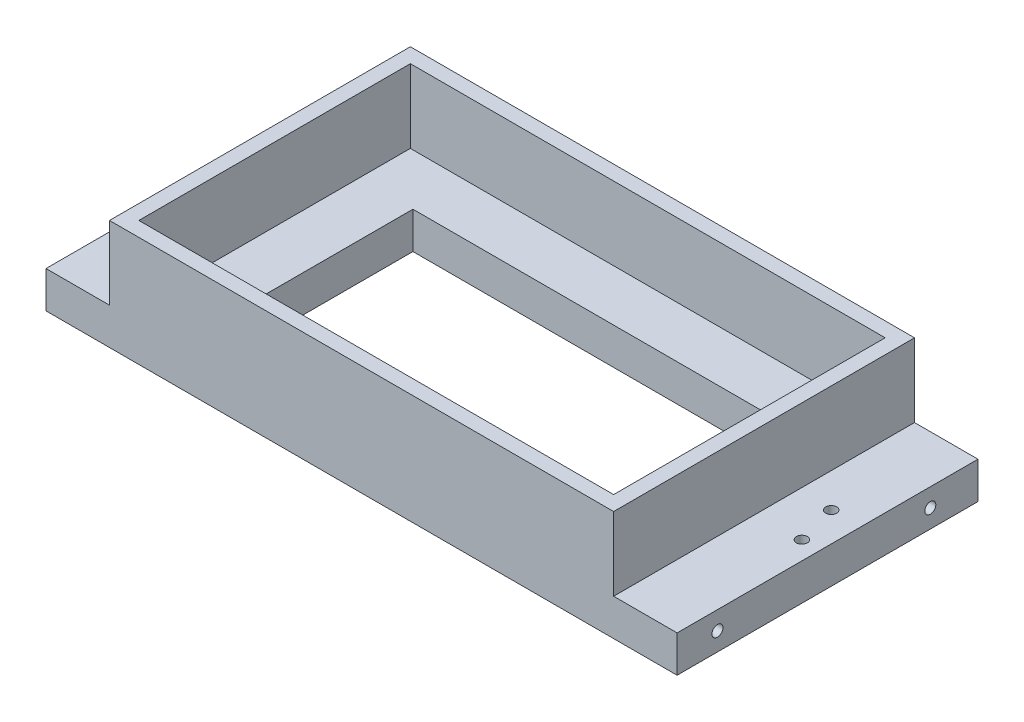
SolidWorks part; units mm, degrees
ref_plane "前视基准面" through (0, 0, 0) normal (0, 0, 1) x (1, 0, 0)
ref_plane "上视基准面" through (0, 0, 0) normal (0, 1, 0) x (1, 0, 0)
ref_plane "右视基准面" through (0, 0, 0) normal (1, 0, 0) x (0, 0, -1)
other "Configuration Table"
sketch "草图1" plane through (0, 0, 0) normal (0, 1, 0) x (1, 0, 0)
  line L1 (-43, -60.5) -> (43, -60.5)
  line L2 (-43, -60.5) -> (-43, 60.5)
  line L3 (-43, 60.5) -> (43, 60.5)
  line L4 (43, -60.5) -> (43, 60.5)
  line L5 (-43, -60.5) -> (43, 60.5) construction
  line L6 (-43, 60.5) -> (43, -60.5) construction
  line L7 (-25, 50.5) -> (25, 50.5)
  line L8 (-25, 50.5) -> (-25, -4.5)
  line L9 (-25, -4.5) -> (25, -4.5)
  line L10 (25, 50.5) -> (25, -4.5)
  line L11 (-25, -25.5) -> (25, -25.5)
  line L12 (-25, -25.5) -> (-25, -50.5)
  line L13 (-25, -50.5) -> (25, -50.5)
  line L14 (25, -25.5) -> (25, -50.5)
  line L15 (-43, -60.5) -> (43, -60.5)
  line L16 (-43, -60.5) -> (-43, -113.5)
  line L17 (-43, -113.5) -> (43, -113.5)
  line L18 (43, -60.5) -> (43, -113.5)
  line L19 (-38, -65.5) -> (38, -65.5)
  line L20 (-38, -65.5) -> (-38, -108.5)
  line L21 (-38, -108.5) -> (38, -108.5)
  line L22 (38, -65.5) -> (38, -108.5)
  point P0 (0, 0)
  dimension "D1" = 86
  dimension "D2" = 121
  dimension "D3" = 10
  dimension "D4" = 18
  dimension "D5" = 18
  dimension "D6" = 55
  dimension "D7" = 10
  dimension "D8" = 25
  dimension "D9" = 5
  dimension "D10" = 5
  dimension "D11" = 5
  dimension "D12" = 5
  dimension "D13" = 53
extrude "凸台-拉伸1" add sketch "草图1" along normal blind 5 contours L18 L1 L16 L17 L19 L22 L21 L20 | L2 L3 L4 L1 | L9 L10 L7 L8 | L11 L14 L13 L12 region at (0, 0, 61.5102)
sketch "草图4" plane through (0, 5, 0) normal (0, 1, 0) x (1, 0, 0)
  line L0 (-43, 60.5) -> (43, 60.5) construction
  line L1 (-34.35, 57.5) -> (34.35, 57.5)
  line L2 (-34.35, 57.5) -> (-34.35, -57.5)
  line L3 (-34.35, -57.5) -> (34.35, -57.5)
  line L4 (34.35, 57.5) -> (34.35, -57.5)
  line L5 (-32.35, -18.5) -> (32.35, -18.5)
  line L6 (-32.35, -18.5) -> (-32.35, -55.5)
  line L7 (-32.35, -55.5) -> (32.35, -55.5)
  line L8 (32.35, -18.5) -> (32.35, -55.5)
  line L9 (32.35, -14.5) -> (-32.35, -14.5)
  line L10 (32.35, -14.5) -> (32.35, 55.5)
  line L11 (32.35, 55.5) -> (-32.35, 55.5)
  line L12 (-32.35, -14.5) -> (-32.35, 55.5)
  line L13 (43, 60.5) -> (43, -113.5) construction
  line L14 (-43, 60.5) -> (-43, -113.5) construction
  dimension "D1" = 5
  dimension "D2" = 10.65
  dimension "D3" = 10.65
  dimension "D4" = 2
  dimension "D5" = 2
  dimension "D6" = 2
  dimension "D7" = 70
  dimension "D8" = 79
  dimension "D9" = 37
  dimension "D10" = 2
extrude "凸台-拉伸2" add sketch "草图4" along normal blind 10 contours L3 L4 L1 L2 | L6 L7 L8 L5 | L12 L11 L10 L9
sketch "草图5" plane through (0, 5, 0) normal (0, 1, 0) x (1, 0, 0)
  line L0 (-43, 60.5) -> (-43, -113.5) construction
  line L1 (43, 60.5) -> (43, -113.5) construction
  line L2 (-43, 60.5) -> (43, 60.5) construction
  line L3 (-43, -85.5) -> (-38, -85.5)
  line L4 (-38, -65.5) -> (-38, -108.5) construction
  line L5 (-23.6333, -57.5) -> (-23.6333, -113.5)
  line L6 (-34.35, -57.5) -> (34.35, -57.5) construction
  line L7 (-43, -113.5) -> (43, -113.5) construction
  line L8 (38, -85.5) -> (43, -85.5)
  line L9 (38, -65.5) -> (38, -108.5) construction
  line L10 (-25, -25.5) -> (-25, -50.5) construction
  line L12 (-34.35, 57.5) -> (34.35, 57.5) construction
  line L13 (-25, -4.5) -> (25, -4.5) construction
  circle A0 centre (-39, 20.5) radius 0.75
  circle A1 centre (39, 20.5) radius 0.75
  circle A2 centre (-39, -32.5) radius 0.75
  circle A3 centre (39, -32.5) radius 0.75
  circle A4 centre (-40.1428, -60.35) radius 0.75
  circle A5 centre (40.1428, -60.35) radius 0.75
  circle A6 centre (-40.1428, -110.5303) radius 0.75
  circle A7 centre (40.1428, -110.5303) radius 0.75
  circle A8 centre (-40.5, 57.5) radius 0.75
  circle A9 centre (-40.5, -38) radius 0.75
  circle A10 centre (-40.5, -85.5) radius 0.75
  circle A11 centre (40.5, 57.5) radius 0.75
  circle A12 centre (40.5, -38) radius 0.75
  circle A13 centre (40.5, -85.5) radius 0.75
  circle A14 centre (-40.5, -4.5) radius 0.75
  circle A15 centre (40.5, -4.5) radius 0.75
  point P40 (-23.6333, -85.5)
  point P52 (-25, -38)
  dimension "D1" = 1.5
  dimension "D2" = 4
  dimension "D3" = 4
  dimension "D4" = 40
  dimension "D5" = 93
extrude "切除-拉伸1" cut sketch "草图5" against normal through all contours A0 | A2 | A4 | A6 | A7 | A5 | A3 | A1 | A8 | A11 | A9 | A12 | A10 | A13 | A14 | A15
sketch "草图7" plane through (0, 5, 0) normal (0, 1, 0) x (1, 0, 0)
  line L0 (42.9928, -57.5) -> (-42.9928, -57.5) construction
  line L1 (-32, -57.5) -> (-17, -57.5)
  line L2 (-32, -57.5) -> (-32, -65.5)
  line L3 (-32, -65.5) -> (-17, -65.5)
  line L4 (-17, -57.5) -> (-17, -65.5)
  line L5 (-43, 60.5) -> (-43, -113.5) construction
  line L6 (-38, -65.5) -> (38, -65.5) construction
  line L8 (-34.35, -57.5) -> (34.35, -57.5) construction
  line L9 (-13, -57.5) -> (13, -57.5)
  line L10 (-13, -57.5) -> (-13, -65.5)
  line L11 (-13, -65.5) -> (13, -65.5)
  line L12 (13, -57.5) -> (13, -65.5)
  line L13 (-38, -65.5) -> (-38, -108.5) construction
  line L14 (-43, -73.5) -> (-38, -73.5)
  line L15 (-43, -73.5) -> (-43, -83.5)
  line L16 (-43, -83.5) -> (-38, -83.5)
  line L17 (-38, -73.5) -> (-38, -83.5)
  line L18 (-43, -113.5) -> (43, -113.5) construction
  line L19 (-43, -95.3803) -> (-38, -95.3803)
  line L20 (-43, -95.3803) -> (-43, -107.5)
  line L21 (-43, -107.5) -> (-38, -107.5)
  line L22 (-38, -95.3803) -> (-38, -107.5)
  line L23 (-42.9928, -113.3803) -> (42.9928, -113.3803) construction
  line L24 (-38, -108.5) -> (38, -108.5) construction
  line L25 (-35, -108.5) -> (-29, -108.5)
  line L26 (-35, -108.5) -> (-35, -113.5)
  line L27 (-35, -113.5) -> (-29, -113.5)
  line L28 (-29, -108.5) -> (-29, -113.5)
  line L29 (43, 60.5) -> (43, -113.5) construction
  line L30 (-6, -108.5) -> (0, -108.5)
  line L31 (-6, -108.5) -> (-6, -113.5)
  line L32 (-6, -113.5) -> (0, -113.5)
  line L33 (0, -108.5) -> (0, -113.5)
  line L34 (14, -108.5) -> (21, -108.5)
  line L35 (14, -108.5) -> (14, -113.5)
  line L36 (14, -113.5) -> (21, -113.5)
  line L37 (21, -108.5) -> (21, -113.5)
  line L38 (27, -108.5) -> (34, -108.5)
  line L39 (27, -108.5) -> (27, -113.5)
  line L40 (27, -113.5) -> (34, -113.5)
  line L41 (34, -108.5) -> (34, -113.5)
  line L42 (43, -81.5) -> (38, -81.5)
  line L43 (43, -81.5) -> (43, -102.5)
  line L44 (43, -102.5) -> (38, -102.5)
  line L45 (38, -81.5) -> (38, -102.5)
  line L46 (38, -65.5) -> (38, -108.5) construction
  dimension "D1" = 11
  dimension "D2" = 26
  dimension "D3" = 30
  dimension "D4" = 56
  dimension "D5" = 16
  dimension "D6" = 26
  dimension "D7" = 6
  dimension "D8" = 18
  dimension "D9" = 8
  dimension "D10" = 14
  dimension "D11" = 37
  dimension "D12" = 43
  dimension "D13" = 57
  dimension "D14" = 64
  dimension "D15" = 70
  dimension "D16" = 77
  dimension "D17" = 11
  dimension "D18" = 32
extrude "切除-拉伸2" cut sketch "草图7" against normal blind 2
sketch "草图8" plane through (-43, 0, 0) normal (-1, 0, 0) x (0, 0, 1)
  line L0 (0, 0) -> (0, 5)
  line L1 (-57.5, 5) -> (57.5, 5) construction
  circle A0 centre (8, 2.5) radius 0.75
  circle A1 centre (23, 2.5) radius 0.75
  circle A2 centre (52, 2.5) radius 0.75
  circle A3 centre (63, 2.5) radius 0.75
  point P13 (0, 2.5)
  dimension "D1" = 1.5
  dimension "D2" = 8
  dimension "D3" = 15
  dimension "D4" = 29
  dimension "D5" = 11
extrude "切除-拉伸3" cut sketch "草图8" against normal blind 2 contours A0 | A1 | A2 | A3
extrude "切除-拉伸4" cut sketch "草图8<3>" along normal blind 2 from surface contours A0 | A1 | A2 | A3 starting at face at (43, 3.25, 59.25)
sketch "草图8<3>" plane through (-43, 0, 0) normal (-1, 0, 0) x (0, 0, 1) same geometry as "草图8"
sketch "草图9" plane through (0, 0, 0) normal (0, 1, 0) x (1, 0, 0)
  line L0 (0, -14.5) -> (0, -18.5)
  line L1 (-47.378, 69.2613) -> (49.394, 69.2613)
  line L2 (-47.378, 69.2613) -> (-47.378, -16.5)
  line L3 (-47.378, -16.5) -> (49.394, -16.5)
  line L4 (49.394, 69.2613) -> (49.394, -16.5)
  line L5 (49.394, -16.5) -> (-47.378, -16.5)
  line L6 (49.394, -16.5) -> (49.394, -57.5)
  line L7 (49.394, -57.5) -> (-47.378, -57.5)
  line L8 (-47.378, -16.5) -> (-47.378, -57.5)
  line L9 (-47.378, -57.5) -> (55.1903, -57.5)
  line L10 (-47.378, -57.5) -> (-47.378, -123.0227)
  line L11 (-47.378, -123.0227) -> (55.1903, -123.0227)
  line L12 (55.1903, -57.5) -> (55.1903, -123.0227)
  line L13 (32.35, -14.5) -> (-32.35, -14.5) construction
  line L14 (-32.35, -18.5) -> (32.35, -18.5) construction
  line L15 (-34.35, -57.5) -> (34.35, -57.5) construction
  point P15 (0, -16.5)
extrude "切除-拉伸5" cut sketch "草图9" along normal through all contours L4 L1 L2 L3 | L12 L9 L7 L10 L11 region at (1.008, 0, -26.3806) region at (3.9062, 0, 90.2614)
